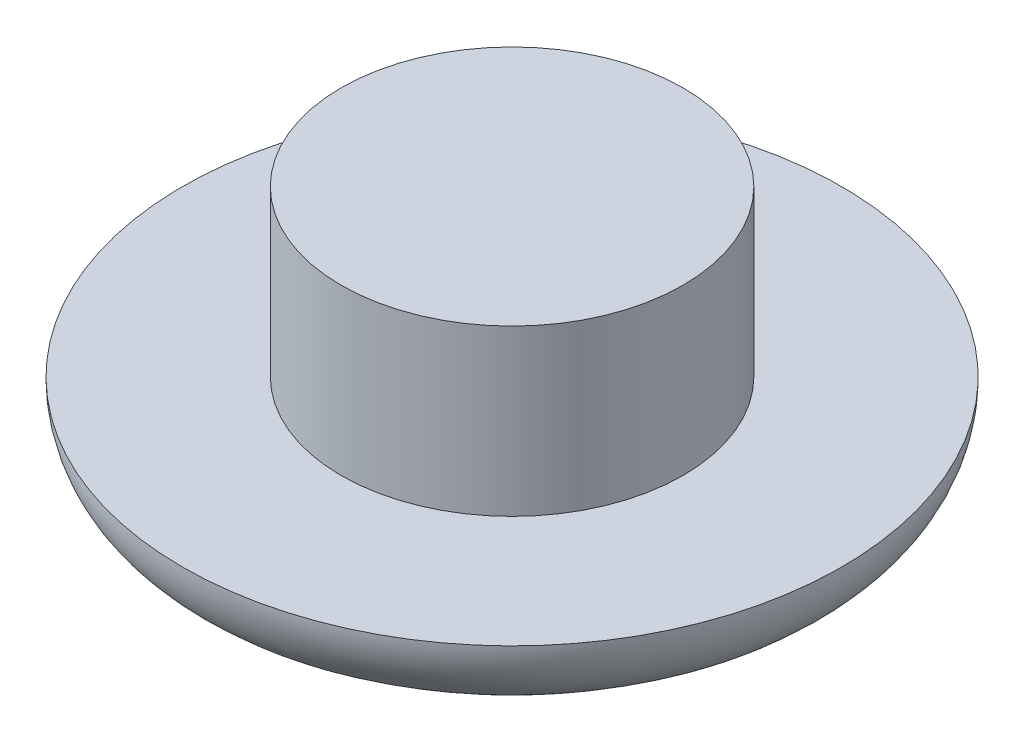
SolidWorks part; units mm, degrees
ref_plane "Front Plane" through (0, 0, 0) normal (0, 0, 1) x (1, 0, 0)
ref_plane "Top Plane" through (0, 0, 0) normal (0, 1, 0) x (1, 0, 0)
ref_plane "Right Plane" through (0, 0, 0) normal (1, 0, 0) x (0, 0, -1)
sketch "base" plane through (0, 0, 0) normal (0, 1, 0) x (1, 0, 0)
  circle A0 centre (0, 0) radius 40
  dimension "D1" = 80
extrude "Boss-Extrude1" add sketch "base" against normal blind 10
sketch "stopper" plane through (0, 0, 0) normal (0, 1, 0) x (1, 0, 0)
  circle A0 centre (0, 0) radius 20.75
  dimension "D1" = 41.5
extrude "Boss-Extrude2" add sketch "stopper" along normal blind 20
fillet "Fillet1" radius 10 1 edges at (0, -10, 40)
